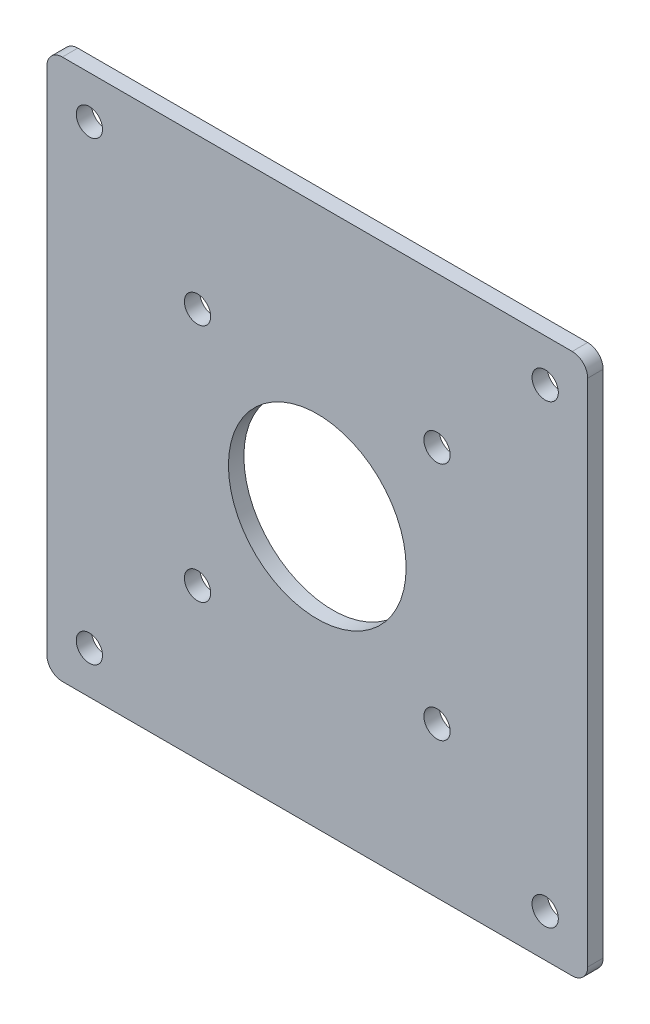
SolidWorks part; units mm, degrees
ref_plane "Vorne" through (0, 0, 0) normal (0, 0, 1) x (1, 0, 0)
ref_plane "Oben" through (0, 0, 0) normal (0, 1, 0) x (1, 0, 0)
ref_plane "Rechts" through (0, 0, 0) normal (1, 0, 0) x (0, 0, -1)
ref_plane "E_Boden" through (0, 1, 0) normal (0, 1, 0) x (1, 0, 0)
sketch "Skizze1" plane through (0, 0, 0) normal (0, 0, 1) x (1, 0, 0)
  line L0 (0, 8.4271) -> (0, -17.0097) construction
  line L1 (-16.4189, 0) -> (17.6005, 0) construction
  line L3 (-35, 35) -> (35, 35)
  line L4 (-35, 35) -> (-35, -35)
  line L5 (-35, -35) -> (35, -35)
  line L6 (35, 35) -> (35, -35)
  dimension "D1" = 70
  dimension "D2" = 70
extrude "Aufsatz-Linear austragen1" add sketch "Skizze1" along normal blind 2
fillet "Verrundung2" radius 2 4 edges at (-35, 35, 1) (-35, -35, 1) (35, -35, 1) (35, 35, 1)
hole_wizard "Ø23.0 (23) Durchmesser Bohrung1" positions "Skizze2" profile "Skizze3" hole size "Ø23.0" standard "DIN" end condition through all
sketch "Skizze2" plane through (0, 0, 2) normal (0, 0, 1) x (1, 0, 0)
  point P0 (0, 0)
sketch "Skizze3" plane through (0, 0, 2) normal (1, 0, 0) x (0, -1, 0)
  line L0 (0, 0) -> (0, 2)
  line L1 (0, 2) -> (11.5, 2)
  line L2 (11.5, 2) -> (11.5, 0)
  line L5 (11.5, 0) -> (0, 0)
  line L11 (0, -6.35) -> (0, 107.95) construction
  dimension "Bohrerdurchmesser" = 23
  dimension "Bohrungstiefe" = 2
hole_wizard "Durchgangsloch für M31" positions "Skizze4" profile "Skizze5" hole size "M3" standard "DIN" end condition through all
sketch "Skizze4" plane through (0, 0, 2) normal (0, 0, 1) x (1, 0, 0)
  line L0 (0, 35) -> (0, -35) construction
  line L1 (33, 35) -> (-33, 35) construction
  line L2 (-33, -35) -> (33, -35) construction
  line L4 (67.0133, -10.5588) -> (66.8256, -10.2773) construction
  line L6 (-35, 0) -> (35, 0) construction
  line L7 (-35, 33) -> (-35, -33) construction
  line L8 (35, -33) -> (35, 33) construction
  point P0 (-15.5, 15.5)
  point P2 (15.5, 15.5)
  point P4 (15.5, -15.5)
  point P6 (-15.5, -15.5)
  dimension "D1" = 31
  dimension "D2" = 31
  dimension "D3" = 31
sketch "Skizze5" plane through (-15.5, 15.5, 2) normal (1, 0, 0) x (0, -1, 0)
  line L0 (0, 0) -> (0, 2)
  line L1 (0, 2) -> (1.7, 2)
  line L2 (1.7, 2) -> (1.7, 0)
  line L5 (1.7, 0) -> (0, 0)
  line L11 (0, -6.35) -> (0, 107.95) construction
  dimension "Bohrerdurchmesser" = 3.4
  dimension "Bohrungstiefe" = 2
hole_wizard "Durchgangsloch für M32" positions "Skizze6" profile "Skizze7" hole size "M3" standard "DIN" end condition through all
sketch "Skizze6" plane through (0, 0, 2) normal (0, 0, 1) x (1, 0, 0)
  line L0 (0, 35) -> (0, -35) construction
  line L1 (33, 35) -> (-33, 35) construction
  line L2 (-33, -35) -> (33, -35) construction
  line L4 (-35, 0) -> (35, 0) construction
  line L5 (-35, 33) -> (-35, -33) construction
  line L6 (35, -33) -> (35, 33) construction
  point P0 (-29.5, 29.5)
  point P2 (29.5, 29.5)
  point P4 (29.5, -29.5)
  point P6 (-29.5, -29.5)
  dimension "D1" = 59
  dimension "D2" = 59
  dimension "D3" = 59
  dimension "D4" = 59
sketch "Skizze7" plane through (-29.5, 29.5, 2) normal (1, 0, 0) x (0, -1, 0)
  line L0 (0, 0) -> (0, 2)
  line L1 (0, 2) -> (1.7, 2)
  line L2 (1.7, 2) -> (1.7, 0)
  line L5 (1.7, 0) -> (0, 0)
  line L11 (0, -6.35) -> (0, 107.95) construction
  dimension "Bohrerdurchmesser" = 3.4
  dimension "Bohrungstiefe" = 2
